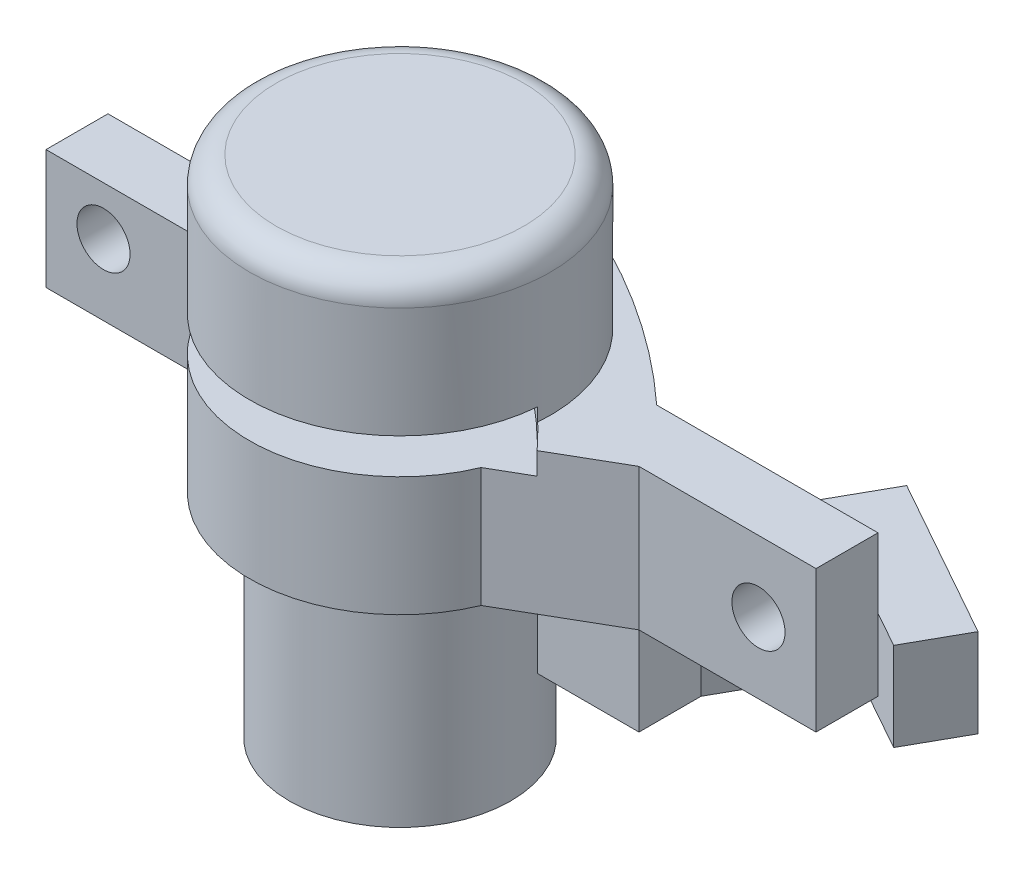
SolidWorks part; units mm, degrees
ref_plane "Front Plane" through (0, 0, 0) normal (0, 0, 1) x (1, 0, 0)
ref_plane "Top Plane" through (0, 0, 0) normal (0, 1, 0) x (1, 0, 0)
ref_plane "Right Plane" through (0, 0, 0) normal (1, 0, 0) x (0, 0, -1)
sketch "Sketch1" plane through (0, 0, 0) normal (0, 1, 0) x (1, 0, 0)
  line L0 (0, -55) -> (0, 55) construction
  line L2 (-55, 0) -> (55, 0) construction
  line L3 (0, 0) -> (23, 0)
  line L4 (0, 0) -> (0, 7)
  line L5 (0, 7) -> (22, 7)
  line L6 (22, 7) -> (20.8133, 20.5642)
  line L7 (87, 0) -> (87, 7)
  line L8 (55.6978, -6.5253) -> (67, 0)
  line L9 (67, 0) -> (87, 0)
  line L10 (87, 7) -> (62, 7)
  arc A0 (23, 0) -> (55.6978, -6.5253) centre (40, 0) ccw
  arc A1 (26.9971, 25.8532) -> (62, 7) centre (7.7519, -51.7975) cw
  arc A2 (26.9971, 25.8532) -> (20.8133, 20.5642) centre (25.7943, 21) ccw
  dimension "D1" = 34
  dimension "D7" = 80
  dimension "D8" = 5
  dimension "D2" = 40
  dimension "D3" = 87
  dimension "D4" = 7
  dimension "D5" = 30
  dimension "D6" = 20
  dimension "D9" = 21
  dimension "D10" = 85
  dimension "D11" = 22
  dimension "D12" = 25
extrude "Boss-Extrude1" add sketch "Sketch1" along normal blind 16
sketch "Sketch2" plane through (0, 16, 0) normal (0, 1, 0) x (1, 0, 0)
  circle A0 centre (40, 0) radius 17
extrude "Boss-Extrude2" add sketch "Sketch2" along normal blind 17
sketch "Sketch3" plane through (0, 0, 0) normal (0, -1, 0) x (1, 0, 0)
  circle A0 centre (40, 0) radius 12.5
  dimension "D1" = 25
extrude "Boss-Extrude3" add sketch "Sketch3" along normal blind 24
sketch "Sketch4" plane through (0, 0, -7) normal (0, 0, -1) x (-1, 0, 0)
  line L0 (-87, 8) -> (0, 8) construction
  line L1 (-87, 16) -> (-87, 0) construction
  line L2 (0, 23.65) -> (0, -23.65) construction
  circle A0 centre (-80.5, 8) radius 3
  circle A1 centre (-6.5, 8) radius 3
  dimension "D1" = 6
  dimension "D2" = 74
  dimension "D3" = 6.5
extrude "Cut-Extrude1" cut sketch "Sketch4" against normal through all
sketch "Sketch5" plane through (0, 0, 0) normal (0, 1, 0) x (1, 0, 0)
  line L0 (67, 7) -> (73.3028, 18.2502)
  line L1 (87, 7) -> (62, 7) construction
  line L3 (68, 29.2448) -> (55.5123, 6.9548)
  line L4 (55.5123, 6.9548) -> (55.5123, 0)
  line L5 (-31.35, 0) -> (31.35, 0) construction
  line L6 (55.5123, 0) -> (67, 0)
  line L7 (67, 0) -> (67, 7)
  line L8 (87, 0) -> (87, 7) construction
  line L10 (86.3208, 18.9808) -> (82.8994, 12.8738)
  line L11 (82.8994, 12.8738) -> (73.3028, 18.2502)
  line L12 (68, 29.2448) -> (86.3208, 18.9808)
  circle A0 centre (40, 0) radius 17 construction
  dimension "D1" = 7
  dimension "D2" = 21
  dimension "D3" = 12
  dimension "D4" = 20
  dimension "D5" = 19
  dimension "D6" = 10
extrude "Boss-Extrude5" add sketch "Sketch5" against normal blind 10
sketch "Sketch7" plane through (0, 13.5, 0) normal (0, 1, 0) x (1, 0, 0)
  circle A0 centre (-0.4, -60) radius 82
  arc A2 (26.6335, -135.294) -> (58.5192, -114.1159) centre (-0.4, -60) ccw construction
  dimension "D1" = 164
extrude "Cut-Extrude2" cut sketch "Sketch7" along normal blind 4
fillet "Fillet1" radius 3 1 edges at (40, 33, 17)
